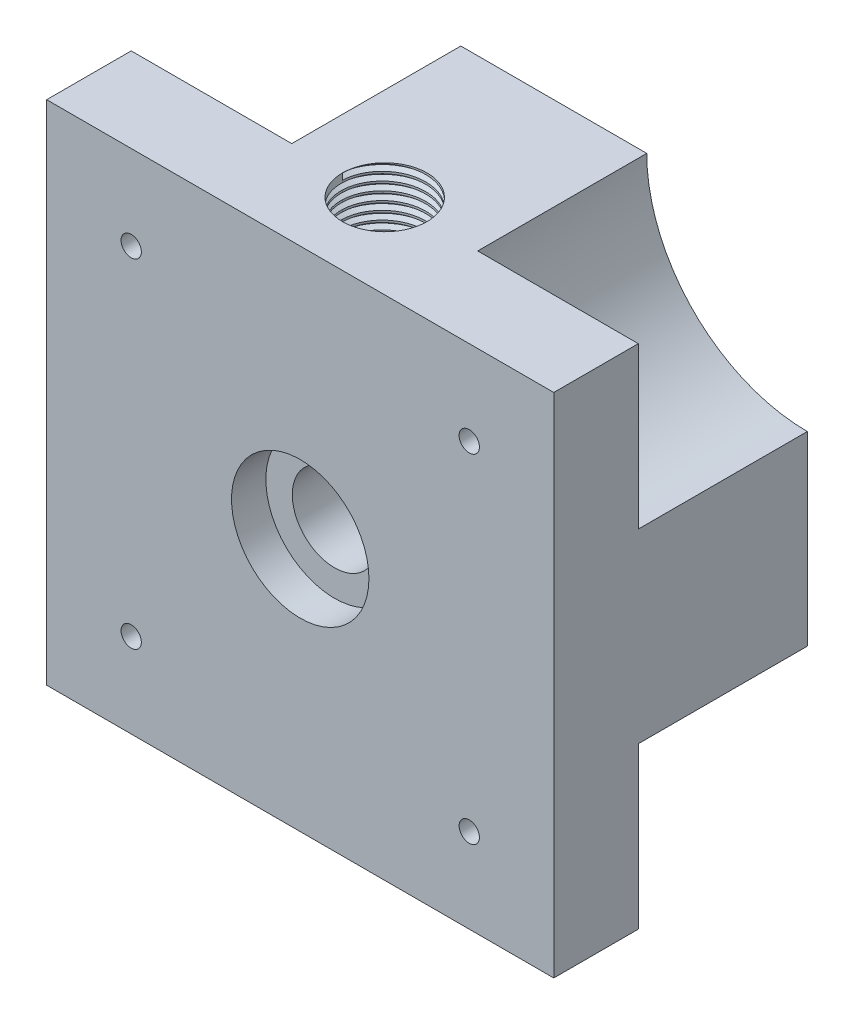
SolidWorks part; units mm, degrees
ref_plane "Front Plane" through (0, 0, 0) normal (0, 0, 1) x (1, 0, 0)
ref_plane "Top Plane" through (0, 0, 0) normal (0, 1, 0) x (1, 0, 0)
ref_plane "Right Plane" through (0, 0, 0) normal (1, 0, 0) x (0, 0, -1)
sketch "Sketch2" plane through (0, 0, 0) normal (0, 0, 1) x (1, 0, 0)
  line L1 (-38.1, -38.1) -> (38.1, -38.1)
  line L2 (-38.1, -38.1) -> (-38.1, 38.1)
  line L3 (-38.1, 38.1) -> (38.1, 38.1)
  line L4 (38.1, -38.1) -> (38.1, 38.1)
  line L5 (-38.1, -38.1) -> (38.1, 38.1) construction
  line L6 (-38.1, 38.1) -> (38.1, -38.1) construction
  point P0 (0, 0)
  dimension "D1" = 76.2
  dimension "D2" = 76.2
extrude "Boss-Extrude1" add sketch "Sketch2" along normal blind 38.1
sketch "Sketch3" plane through (0, 0, 0) normal (0, 0, -1) x (-1, 0, 0)
  circle A0 centre (0, 0) radius 25.4
  dimension "D1" = 50.8
extrude "Cut-Extrude1" cut sketch "Sketch3" against normal blind 12.7
sketch "Sketch4" plane through (0, 0, 12.7) normal (0, 0, -1) x (-1, 0, 0)
  circle A0 centre (0, 0) radius 6.35
  dimension "D1" = 12.7
extrude "Cut-Extrude2" cut sketch "Sketch4" against normal through all
sketch "Sketch5" plane through (0, 38.1, 0) normal (0, 1, 0) x (1, 0, 0)
  line L0 (38.1, 0) -> (-38.1, 0) construction
  circle A0 centre (0, -25.4) radius 6.35
  point P4 (0, 0)
  dimension "D1" = 12.7
  dimension "D2" = 25.4
extrude "Cut-Extrude3" cut sketch "Sketch5" against normal blind 25.4
thread "Thread1" pitch 1.27 method cut profile "Thread Profile2" start angle 0, offset 0, length 12.7, pitch 1.27, diameter 12.7
ref_plane "Plane2" through (-6.35, 38.1, 25.4) normal (0, 0, 1) x (-1, 0, 0)
sketch "Thread Profile2" plane through (-6.35, 38.1, 25.4) normal (0, 0, 1) x (-1, 0, 0)
  line L0 (0, 0) -> (0, 1.27) construction
  line L1 (0, 0) -> (0.6874, 0.3969)
  line L2 (0.6874, 0.3969) -> (0.6874, 0.5556)
  line L3 (0.6874, 0.5556) -> (0, 0.9525)
  line L4 (0.6874, 0.4762) -> (0, 0.4762) construction
  line L11 (0, 0) -> (0, 0.9525)
  point P2 (0, 0)
  dimension "Pitch" = 1.27
  dimension "Profile_Angle" = 60
  dimension "Profile_Land" = 0.1588
  dimension "Profile_Height" = 0.6874
sketch "Sketch17" plane through (0, 0, 38.1) normal (0, 0, 1) x (1, 0, 0)
  line L0 (-38.1, 38.1) -> (-38.1, -38.1) construction
  line L1 (38.1, 38.1) -> (-38.1, 38.1) construction
  circle A0 centre (-25.4, 25.4) radius 1.524
  circle A1 centre (25.4, 25.4) radius 1.524
  circle A2 centre (25.4, -25.4) radius 1.524
  circle A3 centre (-25.4, -25.4) radius 1.524
  point P15 (0, 0)
  dimension "D1" = 3.048
  dimension "D2" = 12.7
  dimension "D3" = 12.7
  dimension "D4" = 4
extrude "Cut-Extrude5" cut sketch "Sketch17" against normal through all
sketch "Sketch18" plane through (0, 0, 38.1) normal (0, 0, 1) x (1, 0, 0)
  circle A0 centre (0, 0) radius 10.3251
  dimension "D1" = 20.6502
extrude "Cut-Extrude6" cut sketch "Sketch18" against normal blind 5.1562
sketch "Sketch19" plane through (0, 0, 12.7) normal (0, 0, -1) x (-1, 0, 0)
  circle A0 centre (0, 15.24) radius 3.175
  circle A1 centre (0, 0) radius 6.35 construction
  dimension "D1" = 6.35
  dimension "D2" = 15.24
extrude "Cut-Extrude7" cut sketch "Sketch19" against normal blind 12.7
sketch "Sketch20" plane through (0, 0, 0) normal (0, 0, -1) x (-1, 0, 0)
  line L0 (-38.1, -38.1) -> (-38.1, 38.1) construction
  circle A0 centre (-38.1, 38.1) radius 24.13
  circle A1 centre (38.1, 38.1) radius 24.13
  circle A2 centre (38.1, -38.1) radius 24.13
  circle A3 centre (-38.1, -38.1) radius 24.13
  point P3 (-25.4, 25.4)
  point P4 (-38.1, 38.1)
  point P12 (0, 0)
  dimension "D1" = 48.26
  dimension "D2" = 4
extrude "Cut-Extrude8" cut sketch "Sketch20" against normal blind 25.4
thread "Thread2" pitch 3.175 method cut profile "Thread Profile3" start angle 0, offset 0, length 12.7, pitch 3.175, diameter 50.8
ref_plane "Plane3" through (25.4, 0, 0) normal (0, -1, 0) x (1, 0, 0)
sketch "Thread Profile3" plane through (25.4, 0, 0) normal (0, -1, 0) x (1, 0, 0)
  line L0 (0, 0) -> (0, 3.175) construction
  line L1 (0, 0) -> (1.7185, 0.9922)
  line L2 (1.7185, 0.9922) -> (1.7185, 1.3891)
  line L3 (1.7185, 1.3891) -> (0, 2.3812)
  line L4 (1.7185, 1.1906) -> (0, 1.1906) construction
  line L11 (0, 0) -> (0, 2.3812)
  point P2 (0, 0)
  dimension "Pitch" = 3.175
  dimension "Profile_Angle" = 60
  dimension "Profile_Land" = 0.3969
  dimension "Profile_Height" = 1.7185
